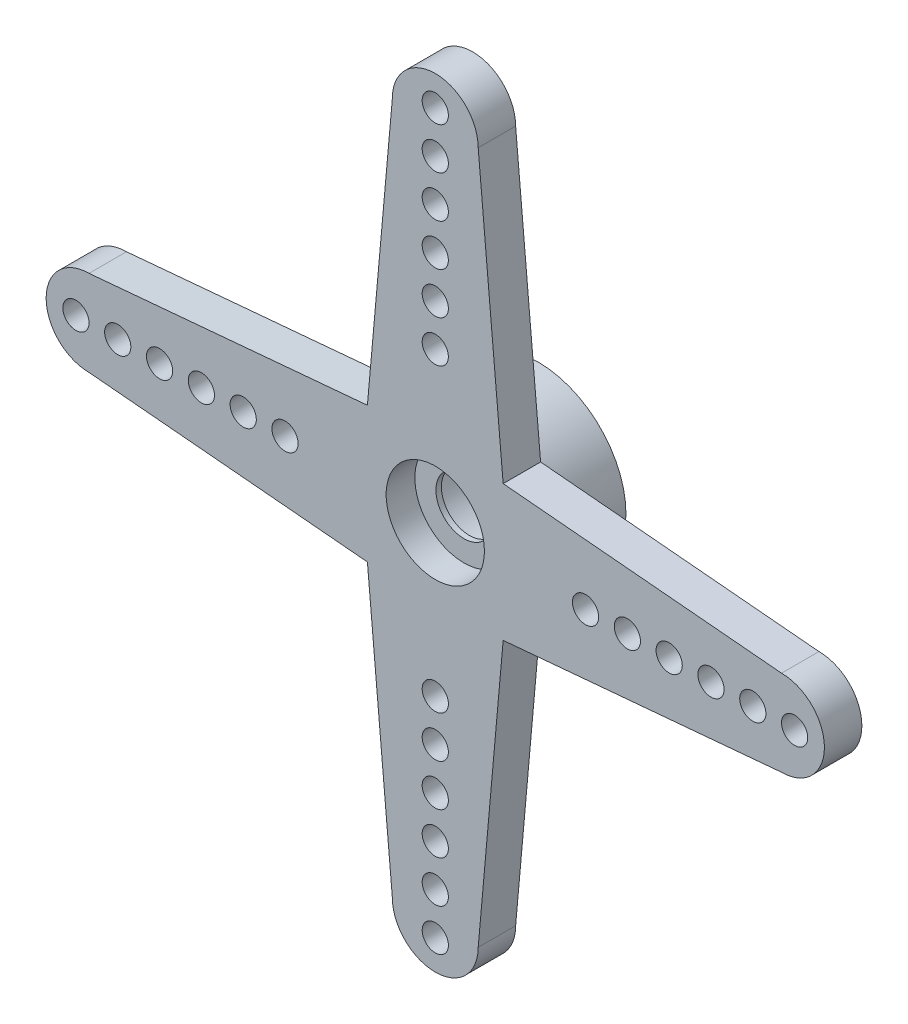
SolidWorks part; units mm, degrees
material "Nylon 6/10"
ref_plane "Front Plane" through (0, 0, 0) normal (0, 0, 1) x (1, 0, 0)
ref_plane "Top Plane" through (0, 0, 0) normal (0, 1, 0) x (1, 0, 0)
ref_plane "Right Plane" through (0, 0, 0) normal (1, 0, 0) x (0, 0, -1)
ref_plane "Plane1" through (0, 0, -7.033) normal (0, 0, 1) x (1, 0, 0)
sketch "Sketch1" plane through (0, 0, -7.033) normal (0, 0, 1) x (1, 0, 0)
  circle A0 centre (-5.5, 0) radius 3.5687
  circle A1 centre (-5.5, 0) radius 2
  dimension "D1" = 7.1374
extrude "Boss-Extrude1" add sketch "Sketch1" along normal blind 4.191
sketch "Sketch5" plane through (0, 0, -4.233) normal (0, 0, 1) x (1, 0, 0)
  circle A0 centre (-5.5, 0) radius 1.143
  circle A1 centre (-5.5, 0) radius 2 construction
  circle A2 centre (-5.5, 0) radius 2
  dimension "D1" = 2.286
extrude "Boss-Extrude2" add sketch "Sketch5" along normal offset from surface (0.2226 mm away) 1.1684 up to face at (-1.9313, 0, -2.842)
sketch "Sketch6" plane through (0, 0, -2.842) normal (0, 0, 1) x (1, 0, 0)
  line L0 (-3.7537, -14.0907) -> (-2.6869, -2.196)
  line L1 (-7.2462, -14.0907) -> (-8.313, -2.196)
  line L2 (-5.5, 0) -> (-5.5, -14.0907) construction
  line L3 (-5.5, -14.6241) -> (-5.5, -12.9223) construction
  arc A0 (-7.2462, -14.0907) -> (-3.7537, -14.0907) centre (-5.5, -14.0907) ccw
  circle A1 centre (-5.5, 0) radius 3.5687 construction
  circle A2 centre (-5.5, 0) radius 3.5687 construction
  circle A3 centre (-5.5, -12.9223) radius 0.5334
  circle A4 centre (-5.5, -14.6241) radius 0.5334
  circle A5 centre (-5.5, -11.2205) radius 0.5334
  circle A6 centre (-5.5, -9.5186) radius 0.5334
  circle A7 centre (-5.5, -7.8169) radius 0.5334
  circle A8 centre (-5.5, -6.1151) radius 0.5334
  arc A9 (-2.6869, -2.196) -> (-8.313, -2.196) centre (-5.5, 0) cw
  dimension "D1" = 3.4925
  dimension "D2" = 15.8369
  dimension "D4" = 1.0668
  dimension "D3" = 5.6261
  dimension "D6" = 1.7018
  dimension "D5" = 6
extrude "Boss-Extrude3" add sketch "Sketch6" against normal blind 1.524
pattern_circular "CirPattern1" count 4 over 360 about axis through (-5.5, 0, -2.842) along (0, 0, -1) of "Boss-Extrude3" reverse direction yes
